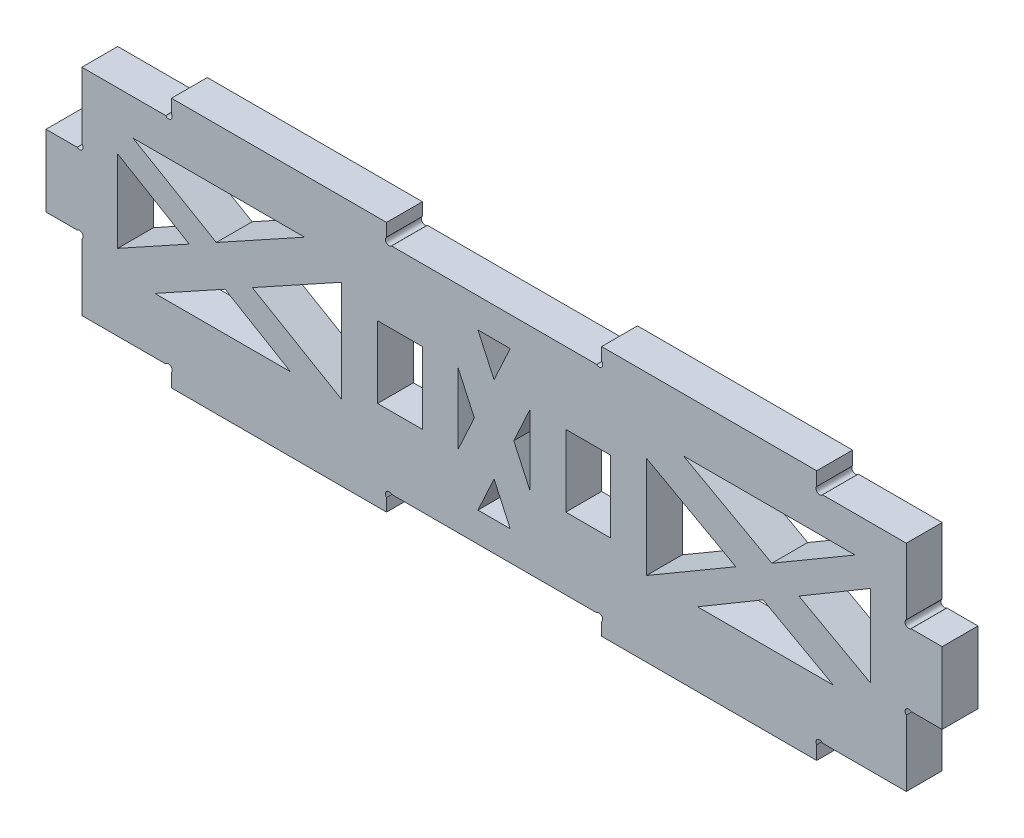
SolidWorks part; units mm, degrees
material "7050-T73510"
ref_plane "Front Plane" through (0, 0, 0) normal (0, 0, 1) x (1, 0, 0)
ref_plane "Top Plane" through (0, 0, 0) normal (0, 1, 0) x (1, 0, 0)
ref_plane "Right Plane" through (0, 0, 0) normal (1, 0, 0) x (0, 0, -1)
sketch "Sketch1" plane through (0, 0, 0) normal (0, 0, 1) x (1, 0, 0)
  line L1 (-158.75, -38.1) -> (158.75, -38.1)
  line L2 (-158.75, -38.1) -> (-158.75, 38.1)
  line L3 (-158.75, 38.1) -> (158.75, 38.1)
  line L4 (158.75, -38.1) -> (158.75, 38.1)
  line L5 (-158.75, -38.1) -> (158.75, 38.1) construction
  line L6 (-158.75, 38.1) -> (158.75, -38.1) construction
  point P0 (0, 0)
  dimension "D1" = 317.5
  dimension "D2" = 76.2
extrude "Boss-Extrude1" add sketch "Sketch1" along normal blind 12.7 contours L1 L3 region at (0, 0, 0)
sketch "Sketch2" plane through (0, 0, 12.7) normal (0, 0, 1) x (1, 0, 0)
  line L0 (-158.75, -38.1) -> (158.75, -38.1) construction
  line L1 (-38.1, -38.1) -> (-114.3, -38.1)
  line L2 (-38.1, -38.1) -> (-38.1, -44.45)
  line L3 (-38.1, -44.45) -> (-114.3, -44.45)
  line L4 (-114.3, -38.1) -> (-114.3, -44.45)
  line L5 (0, -55) -> (0, 55) construction
  line L6 (38.1, -44.45) -> (114.3, -44.45)
  line L7 (114.3, -38.1) -> (114.3, -44.45)
  line L8 (38.1, -38.1) -> (114.3, -38.1)
  line L9 (38.1, -38.1) -> (38.1, -44.45)
  line L10 (55, 0) -> (-55, 0) construction
  line L11 (38.1, 38.1) -> (38.1, 44.45)
  line L12 (38.1, 38.1) -> (114.3, 38.1)
  line L13 (114.3, 38.1) -> (114.3, 44.45)
  line L14 (38.1, 44.45) -> (114.3, 44.45)
  line L15 (-38.1, 44.45) -> (-114.3, 44.45)
  line L16 (-114.3, 38.1) -> (-114.3, 44.45)
  line L17 (-38.1, 38.1) -> (-114.3, 38.1)
  line L18 (-38.1, 38.1) -> (-38.1, 44.45)
  point P12 (-38.1, -41.275)
  dimension "D1" = 76.2
  dimension "D2" = 6.35
  dimension "D3" = 76.2
extrude "Boss-Extrude2" add sketch "Sketch2" against normal blind 12.7
sketch "Sketch3" plane through (0, 0, 12.7) normal (0, 0, 1) x (1, 0, 0)
  line L0 (55, 0) -> (-55, 0) construction
  line L1 (-158.75, -38.1) -> (-146.05, -38.1)
  line L2 (-158.75, -38.1) -> (-158.75, -12.7)
  line L3 (-158.75, -12.7) -> (-146.05, -12.7)
  line L4 (-146.05, -38.1) -> (-146.05, -12.7)
  line L6 (-158.75, 12.7) -> (-146.05, 12.7)
  line L7 (-146.05, 38.1) -> (-146.05, 12.7)
  line L8 (-158.75, 38.1) -> (-146.05, 38.1)
  line L9 (-158.75, 38.1) -> (-158.75, 12.7)
  line L10 (0, -55) -> (0, 55) construction
  line L11 (158.75, 38.1) -> (158.75, 12.7)
  line L12 (158.75, 38.1) -> (146.05, 38.1)
  line L13 (146.05, 38.1) -> (146.05, 12.7)
  line L14 (158.75, 12.7) -> (146.05, 12.7)
  line L15 (158.75, -12.7) -> (146.05, -12.7)
  line L16 (146.05, -38.1) -> (146.05, -12.7)
  line L17 (158.75, -38.1) -> (146.05, -38.1)
  line L18 (158.75, -38.1) -> (158.75, -12.7)
  line L19 (25.4, 12.7) -> (41.275, 12.7)
  line L20 (25.4, 12.7) -> (25.4, -12.7)
  line L21 (25.4, -12.7) -> (41.275, -12.7)
  line L22 (41.275, 12.7) -> (41.275, -12.7)
  line L23 (-38.1, -38.1) -> (38.1, -38.1) construction
  line L24 (-25.4, -12.7) -> (-41.275, -12.7)
  line L25 (-41.275, 12.7) -> (-41.275, -12.7)
  line L26 (-25.4, 12.7) -> (-41.275, 12.7)
  line L27 (-25.4, 12.7) -> (-25.4, -12.7)
  line L28 (-38.1, 38.1) -> (38.1, 38.1) construction
  dimension "D1" = 25.4
  dimension "D2" = 12.7
  dimension "D3" = 50.8
  dimension "D4" = 15.875
  dimension "D5" = 25.4
  dimension "D6" = 25.4
extrude "Cut-Extrude1" cut sketch "Sketch3" against normal through all
sketch "Sketch4" plane through (0, 0, 12.7) normal (0, 0, 1) x (1, 0, 0)
  line L0 (55, 0) -> (-55, 0) construction
  line L1 (-133.35, -18.3931) -> (-53.975, -18.3931)
  line L2 (-133.35, -18.3931) -> (-133.35, 25.4)
  line L3 (-133.35, 25.4) -> (-53.975, 25.4)
  line L4 (-53.975, -18.3931) -> (-53.975, 25.4)
  line L5 (-133.35, -18.3931) -> (-101.6504, -0.9037) construction
  line L6 (0, -55) -> (0, 55) construction
  line L7 (-146.05, 12.7) -> (-146.05, 38.1) construction
  line L8 (-41.275, 12.7) -> (-41.275, -12.7) construction
  line L9 (-146.05, 38.1) -> (-114.3, 38.1) construction
  line L10 (-133.35, 17.8609) -> (-107.9917, 2.85)
  line L11 (-120.2051, -18.3931) -> (-95.3091, -4.6574)
  line L12 (-127.9201, 25.4) -> (-98.411, 8.136)
  line L13 (-133.35, -11.1407) -> (-107.9917, 2.85)
  line L14 (-130.2825, -23.953) -> (-50.9075, 19.8401) construction
  line L15 (-136.4175, -12.8332) -> (-57.0425, 30.9599) construction
  line L16 (100.0125, 0) -> (93.9285, 3.3567) construction
  line L17 (133.35, -18.3931) -> (101.6504, -0.9037) construction
  line L18 (-98.411, 8.136) -> (-67.1199, 25.4)
  line L19 (85.6513, 0.6711) -> (53.975, -17.8609)
  line L20 (-100.0125, 0) -> (-93.9285, 3.3567) construction
  line L21 (-133.35, -18.3931) -> (-53.975, 25.4) construction
  line L22 (-85.6513, 0.6711) -> (-53.975, 18.1476)
  line L23 (-95.3091, -4.6574) -> (-72.1049, -18.3931)
  line L24 (-85.6513, 0.6711) -> (-53.975, -17.8609)
  line L25 (95.3091, -4.6574) -> (72.1049, -18.3931)
  line L26 (85.6513, 0.6711) -> (53.975, 18.1476)
  line L27 (98.411, 8.136) -> (67.1199, 25.4)
  line L28 (133.35, -11.1407) -> (107.9917, 2.85)
  line L29 (127.9201, 25.4) -> (98.411, 8.136)
  line L30 (120.2051, -18.3931) -> (95.3091, -4.6574)
  line L31 (133.35, 17.8609) -> (107.9917, 2.85)
  line L32 (53.975, -18.3931) -> (53.975, 25.4)
  line L33 (133.35, 25.4) -> (53.975, 25.4)
  line L34 (133.35, -18.3931) -> (133.35, 25.4)
  line L35 (133.35, -18.3931) -> (53.975, -18.3931)
  line L36 (-25.4, -12.7) -> (-25.4, 12.7) construction
  line L41 (-12.7, 12.4271) -> (5.7115, -27.6329)
  line L42 (-12.7, -27.6329) -> (12.7, -27.6329)
  line L44 (-12.7, -27.6329) -> (-12.7, 27.6329)
  line L45 (-12.7, 27.6329) -> (12.7, 27.6329)
  line L46 (12.7, -27.6329) -> (12.7, 27.6329)
  line L47 (-12.7, -27.6329) -> (12.7, 27.6329) construction
  line L48 (-12.7, 27.6329) -> (12.7, -27.6329) construction
  line L49 (-5.7115, -27.6329) -> (12.7, 12.4271)
  line L50 (-5.7115, 27.6329) -> (12.7, -12.4271)
  line L51 (-12.7, -12.4271) -> (5.7115, 27.6329)
  line L52 (-6.9302, -30.2847) -> (18.4698, 24.9812) construction
  line L53 (-18.4698, -24.9812) -> (6.9302, 30.2847) construction
  line L54 (-18.4698, 24.9812) -> (6.9302, -30.2847) construction
  line L55 (-6.9302, 30.2847) -> (18.4698, -24.9812) construction
  point P0 (-100.0125, 0)
  point P53 (100.0125, 0)
  point P54 (0, 0)
  dimension "D1" = 12.7
  dimension "D2" = 12.7
  dimension "D3" = 12.7
  dimension "D6" = 12.7
  dimension "D7" = 6.35
  dimension "D4" = 6.35
  dimension "D5" = 6.35
  dimension "D8" = 6.35
extrude "Cut-Extrude2" cut sketch "Sketch4" against normal through all contours L22 L24 L4 | L2 L13 L10 | L12 L18 L3 | L23 L11 L1 | L32 L19 L26 | L35 L30 L25 | L29 L33 L27 | L28 L34 L31 | L45 | L44 | L46 | L42 region at (-95.873, -13.8145, 12.7) region at (-124.8972, 3.1901, 12.7) region at (-64.5338, 0.3193, 12.7) region at (-97.817, 19.6453, 12.7) region at (64.5338, 0.3193, 12.7) region at (95.873, -13.8145, 12.7) region at (97.817, 19.6453, 12.7) region at (124.8972, 3.1901, 12.7) region at (-10.7962, 0, 12.7) region at (0, -23.4906, 12.7) region at (0, 23.4906, 12.7) region at (10.7962, 0, 12.7)
sketch "Sketch7" plane through (0, 0, 12.7) normal (0, 0, 1) x (1, 0, 0)
  line L0 (0, -6.985) -> (0, 6.985) construction
  line L1 (6.985, 0) -> (-6.985, 0) construction
  circle A1 centre (-115.3222, -38.8536) radius 1.27
  circle A2 centre (-37.2199, -39.0156) radius 1.27
  circle A3 centre (37.2199, -39.0156) radius 1.27
  circle A4 centre (115.3222, -38.8536) radius 1.27
  circle A7 centre (115.3222, 38.8536) radius 1.27
  circle A8 centre (37.2199, 39.0156) radius 1.27
  circle A9 centre (-37.2199, 39.0156) radius 1.27
  circle A10 centre (-115.3222, 38.8536) radius 1.27
  circle A12 centre (-146.8896, -13.6529) radius 1.27
  circle A15 centre (-146.8896, 13.6529) radius 1.27
  circle A16 centre (146.8896, -13.6529) radius 1.27
  circle A17 centre (146.8896, 13.6529) radius 1.27
  point P29 (146.8896, 13.6529)
  dimension "D1" = 2.54
  dimension "D2" = 2.54
extrude "Cut-Extrude4" cut sketch "Sketch7" against normal through all
